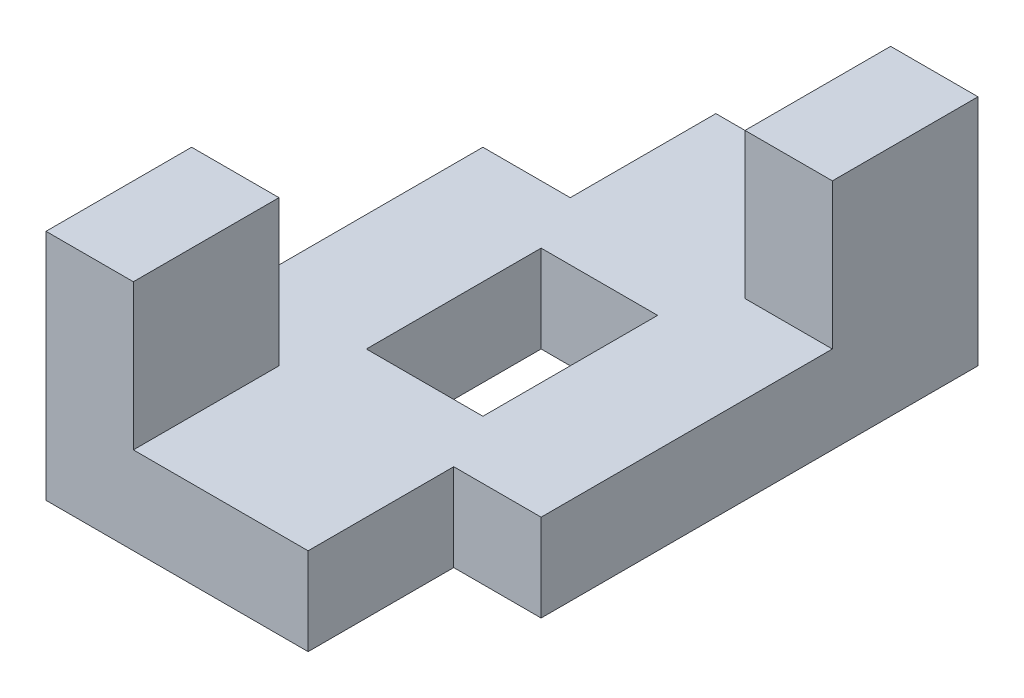
SolidWorks part; units mm, degrees
ref_plane "Front Plane" through (0, 0, 0) normal (0, 0, 1) x (1, 0, 0)
ref_plane "Top Plane" through (0, 0, 0) normal (0, 1, 0) x (1, 0, 0)
ref_plane "Right Plane" through (0, 0, 0) normal (1, 0, 0) x (0, 0, -1)
sketch "Sketch1" plane through (0, 0, 0) normal (0, 1, 0) x (1, 0, 0)
  line L0 (0, 0) -> (0, 25)
  line L1 (0, 25) -> (15, 25)
  line L2 (15, 25) -> (15, 100)
  line L3 (15, 100) -> (-30, 100)
  line L4 (-30, 100) -> (-30, 75)
  line L5 (-30, 75) -> (-45, 75)
  line L6 (-45, 75) -> (-45, 0)
  line L7 (-45, 0) -> (0, 0)
  line L9 (-5, 35) -> (-5, 65)
  line L10 (-5, 35) -> (-25, 35)
  line L11 (-25, 35) -> (-25, 65)
  line L12 (-5, 65) -> (-25, 65)
  line L13 (-5, 35) -> (-25, 65) construction
  line L14 (-25, 35) -> (-5, 65) construction
  line L15 (-45, 0) -> (-45, 25)
  line L16 (-45, 0) -> (-30, 0)
  line L17 (-30, 0) -> (-30, 25)
  line L18 (-45, 25) -> (-30, 25)
  line L19 (15, 100) -> (15, 75)
  line L20 (15, 100) -> (0, 100)
  line L21 (0, 100) -> (0, 75)
  line L22 (15, 75) -> (0, 75)
  point P2 (0, 0)
  point P6 (-15, 50)
  point P15 (-15, 35)
  point P21 (-4.9989, 0.5151)
  point P22 (-54.6687, 23.4383)
  point P23 (0, 0)
  point P24 (0, 0)
  point P26 (-30.6211, 100.0009)
  point P27 (-45, 25)
  point P28 (-30, 0)
  point P29 (0, 0)
  point P30 (0, 0)
  point P31 (0, 0)
  point P32 (0, 0)
  dimension "D1" = 60
  dimension "D2" = 75
  dimension "D3" = 25
  dimension "D4" = 15
  dimension "D5" = 35
  dimension "D6" = 20
  dimension "D7" = 30
  dimension "D8" = 20
  dimension "D9" = 25
  dimension "D10" = 15
extrude "Boss-Extrude1" add sketch "Sketch1" along normal blind 15 contours L2 L22 L21 L3 L4 L5 L6 L18 L17 L7 L0 L1 L12 L9 L10 L11 region at (-15, 0, -1.1662)
extrude "Boss-Extrude2" add sketch "Sketch1<3>" along normal blind 40 contours L22 L2 L3 L21 | L18 L6 L7 L17 region at (-37.5, 0, -12.5) region at (7.5, 0, -87.5)
sketch "Sketch1<3>" plane through (0, 0, 0) normal (0, 1, 0) x (1, 0, 0) same geometry as "Sketch1"
